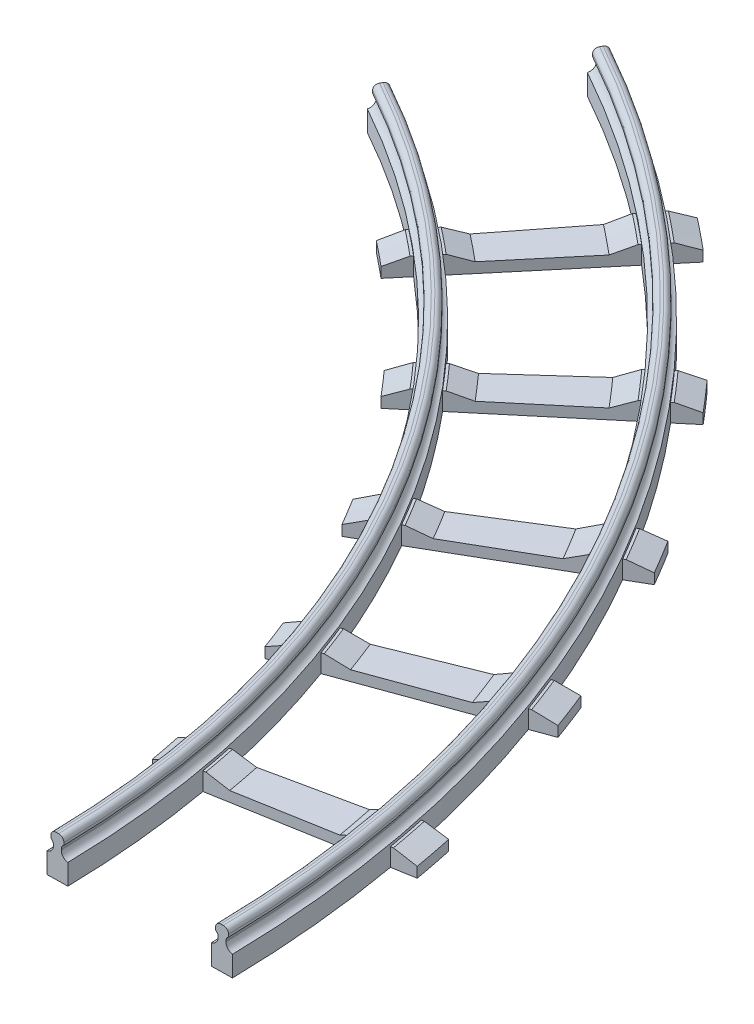
SolidWorks part; units mm, degrees
other "标注1"
sketch "草图3" plane through (-22.25, 4, -10) normal (-0.231, 0.6469, -0.7268) x (-0.9696, -0.2151, 0.1167)
other "标注2"
sketch "草图4" plane through (22.25, 8, -30) normal (0.0083, 0.0567, -0.9984) x (-0.9991, 0.0415, -0.0059)
ref_plane "前视基准面" through (0, 0, 0) normal (0, 0, 1) x (1, 0, 0)
ref_plane "上视基准面" through (0, 0, 0) normal (0, 1, 0) x (1, 0, 0)
ref_plane "右视基准面" through (0, 0, 0) normal (1, 0, 0) x (0, 0, -1)
other "Configuration Table"
sketch "草图1" plane through (0, 0, 0) normal (0, 1, 0) x (1, 0, 0)
  line L0 (-13.75, 14.5) -> (-13.75, -14.5)
  line L13 (-17.75, -14.5) -> (17.75, -14.5)
  line L21 (-17.75, -14.5) -> (-17.75, 14.5)
  line L22 (-17.75, 14.5) -> (17.75, 14.5)
  line L23 (17.75, -14.5) -> (17.75, 14.5)
  line L24 (-17.75, -14.5) -> (17.75, 14.5) construction
  line L25 (-17.75, 14.5) -> (17.75, -14.5) construction
  line L27 (13.75, 14.5) -> (13.75, -14.5)
  line L29 (-13.75, 0) -> (13.75, 0) construction
  line L32 (-22.25, 14.5) -> (22.25, 14.5)
  line L33 (-22.25, 14.5) -> (-22.25, 6.5)
  line L34 (-22.25, 6.5) -> (22.25, 6.5)
  line L35 (22.25, 14.5) -> (22.25, 6.5)
  point P0 (0, 0)
  point P15 (0, 6.5)
  dimension "D3" = 27.5
  dimension "D4" = 8
  dimension "D1" = 35.5
  dimension "D2" = 29
  dimension "D5" = 44.5
extrude "凸台-拉伸1" add sketch "草图1" along normal blind 4 contours L34 L21 L13 L0 | L34 L27 L13 L23 | L27 L34 L23 L22 | L21 L34 L0 L22 region at (-15.75, 0, -10.5) region at (-15.75, 0, 4) region at (15.75, 0, -10.5) region at (15.75, 0, 4)
extrude "凸台-拉伸2" add sketch "草图1<7>" along normal blind 3.5 contours L34 L35 L32 L33
sketch "草图1<7>" plane through (0, 0, 0) normal (0, 1, 0) x (1, 0, 0) same geometry as "草图1"
sketch "草图2" plane through (0, 0, -14.5) normal (0, 0, -1) x (-1, 0, 0)
  line L0 (18.25, 3.5) -> (22.25, 2)
  line L1 (22.25, 3.5) -> (18.25, 3.5)
  line L2 (22.25, 3.5) -> (22.25, 2)
  line L3 (22.25, 2) -> (18.25, 2) construction
  line L4 (18.25, 3.5) -> (18.25, 2) construction
  line L5 (-22.25, 2) -> (-18.25, 3.5)
  line L6 (-22.25, 3.5) -> (-18.25, 3.5)
  line L7 (-22.25, 3.5) -> (-22.25, 2)
  line L8 (-22.25, 2) -> (-18.25, 2) construction
  line L9 (-18.25, 3.5) -> (-18.25, 2) construction
  line L10 (13.75, 3.5) -> (-13.75, 3.5) construction
  line L11 (-13.25, 3.5) -> (-9.25, 3.5)
  line L12 (-13.25, 3.5) -> (-13.25, 2) construction
  line L13 (-13.25, 2) -> (-9.25, 2) construction
  line L14 (-9.25, 3.5) -> (-9.25, 2)
  line L15 (-13.75, 3.5) -> (-13.25, 3.5) construction
  line L16 (13.25, 3.5) -> (9.25, 3.5)
  line L17 (13.25, 3.5) -> (13.25, 2) construction
  line L18 (13.25, 2) -> (9.25, 2) construction
  line L19 (9.25, 3.5) -> (9.25, 2)
  line L20 (13.25, 3.5) -> (13.75, 3.5) construction
  line L21 (17.75, 3.5) -> (18.25, 3.5) construction
  line L22 (-13.25, 3.5) -> (-9.25, 2)
  line L23 (9.25, 2) -> (13.25, 3.5)
  line L24 (-9.25, 2) -> (9.25, 2)
  line L25 (-9.25, 3.5) -> (9.25, 3.5)
  line L26 (-15.75, 4) -> (-15.75, 6.5) construction
  line L27 (14.5, 8) -> (17, 8)
  line L28 (14.5, 8) -> (14.5, 6.5)
  line L29 (14.5, 6.5) -> (17, 6.5)
  line L30 (17, 8) -> (17, 6.5)
  line L31 (-17, 8) -> (-14.5, 8)
  line L32 (-17, 8) -> (-17, 6.5)
  line L33 (-17, 6.5) -> (-14.5, 6.5)
  line L34 (-14.5, 8) -> (-14.5, 6.5)
  line L35 (-13.75, 4) -> (-17.75, 4) construction
  line L36 (15.75, 6.5) -> (15.75, 4) construction
  line L37 (17.75, 4) -> (13.75, 4) construction
  line L38 (15, 6.5) -> (15, 4)
  line L39 (16.5, 6.5) -> (16.5, 4)
  line L40 (16.5, 4) -> (15.75, 4)
  line L41 (15.75, 4) -> (15, 4)
  line L42 (-16.5, 6.5) -> (-16.5, 4)
  line L43 (-16.5, 4) -> (-15.75, 4)
  line L44 (-15.75, 4) -> (-15, 4)
  line L45 (-15, 4) -> (-15, 6.5)
  line M9 (22.25, 3.5) -> (17.75, 3.5)
  line M11 (17.75, 4) -> (13.75, 4)
  line M13 (13.75, 3.5) -> (-13.75, 3.5)
  line M15 (-13.75, 4) -> (-17.75, 4)
  line M17 (-17.75, 3.5) -> (-22.25, 3.5)
  line M18 (-22.25, 3.5) -> (-22.25, 0)
  line M20 (22.25, 0) -> (22.25, 3.5)
  dimension "D1" = 4
  dimension "D2" = 1.5
  dimension "D3" = 2.5
  dimension "D4" = 1.5
  dimension "D5" = 2.5
  dimension "D6" = 1.5
extrude "切除-拉伸1" cut sketch "草图2" against normal through all contours L14 L24 L19 M13 | L19 L23 M13 | L22 L14 M13 | L5 M18 M17 | L0 M9 M20 region at (-20.9167, 3, -14.5) region at (20.9167, 3, -14.5) region at (10.5833, 3, -14.5) region at (0, 2.75, -14.5) region at (-10.5833, 3, -14.5)
extrude "凸台-拉伸4" add sketch "草图2<3>" against normal through all contours L34 L31 L32 L33 | L45 L33 L42 M15 | L30 L27 L28 L29 | L39 L29 L38 M11 region at (-15.75, 7.25, -14.5) region at (-15.75, 5.25, -14.5) region at (15.75, 7.25, -14.5) region at (15.75, 5.25, -14.5)
sketch "草图2<3>" plane through (0, 0, -14.5) normal (0, 0, -1) x (-1, 0, 0) same geometry as "草图2"
fillet "圆角1" radius 1 4 edges at (-16.5, 6.5, 0) (-15, 6.5, 0) (15, 6.5, 0) (16.5, 6.5, 0)
fillet "圆角2" radius 1.5 4 edges at (16.5, 4, 0) (15, 4, 0) (-15, 4, 0) (-16.5, 4, 0)
fillet "圆角3" radius 1 4 edges at (-17, 8, 0) (14.5, 8, 0) (17, 8, 0) (-14.5, 8, 0)
sketch "草图5" plane through (0, 0, -14.5) normal (0, 0, -1) x (-1, 0, 0)
  line L26 (17, 6.5) -> (17, 7)
  line L27 (16, 8) -> (15.5, 8)
  line L28 (14.5, 7) -> (14.5, 6.5)
  line L29 (15, 5.634) -> (15, 5.479)
  line L30 (13.75, 4) -> (13.75, 3.5)
  line L31 (13.75, 3.5) -> (13.25, 3.5)
  line L32 (13.25, 3.5) -> (9.25, 2)
  line L33 (9.25, 2) -> (-9.25, 2)
  line L34 (-9.25, 2) -> (-13.25, 3.5)
  line L35 (-13.25, 3.5) -> (-13.75, 3.5)
  line L36 (-13.75, 3.5) -> (-13.75, 4)
  line L37 (-15, 5.479) -> (-15, 5.634)
  line L38 (-14.5, 6.5) -> (-14.5, 7)
  line L39 (-15.5, 8) -> (-16, 8)
  line L40 (-17, 7) -> (-17, 6.5)
  line L41 (-16.5, 5.634) -> (-16.5, 5.479)
  line L42 (-17.75, 4) -> (-17.75, 3.5)
  line L43 (-17.75, 3.5) -> (-18.25, 3.5)
  line L44 (-18.25, 3.5) -> (-22.25, 2)
  line L45 (-22.25, 2) -> (-22.25, 0)
  line L46 (-22.25, 0) -> (22.25, 0)
  line L47 (22.25, 0) -> (22.25, 2)
  line L48 (22.25, 2) -> (18.25, 3.5)
  line L49 (18.25, 3.5) -> (17.75, 3.5)
  line L50 (17.75, 3.5) -> (17.75, 4)
  line L51 (16.5, 5.479) -> (16.5, 5.634)
  line L52 (17, 6.5) -> (17, 7)
  line L53 (16, 8) -> (15.5, 8)
  line L54 (14.5, 7) -> (14.5, 6.5)
  line L55 (15, 5.634) -> (15, 5.479)
  line L56 (13.75, 4) -> (13.75, 3.5)
  line L57 (13.75, 3.5) -> (13.25, 3.5)
  line L58 (13.25, 3.5) -> (9.25, 2)
  line L59 (9.25, 2) -> (-9.25, 2)
  line L60 (-9.25, 2) -> (-13.25, 3.5)
  line L61 (-13.25, 3.5) -> (-13.75, 3.5)
  line L62 (-13.75, 3.5) -> (-13.75, 4)
  line L63 (-15, 5.479) -> (-15, 5.634)
  line L64 (-14.5, 6.5) -> (-14.5, 7)
  line L65 (-15.5, 8) -> (-16, 8)
  line L66 (-17, 7) -> (-17, 6.5)
  line L67 (-16.5, 5.634) -> (-16.5, 5.479)
  line L68 (-17.75, 4) -> (-17.75, 3.5)
  line L69 (-17.75, 3.5) -> (-18.25, 3.5)
  line L70 (-18.25, 3.5) -> (-22.25, 2)
  line L71 (-22.25, 2) -> (-22.25, 0)
  line L72 (-22.25, 0) -> (22.25, 0)
  line L73 (22.25, 0) -> (22.25, 2)
  line L74 (22.25, 2) -> (18.25, 3.5)
  line L75 (18.25, 3.5) -> (17.75, 3.5)
  line L76 (17.75, 3.5) -> (17.75, 4)
  line L77 (16.5, 5.479) -> (16.5, 5.634)
  arc A12 (17, 7) -> (16, 8) centre (16, 7) ccw
  arc A13 (15.5, 8) -> (14.5, 7) centre (15.5, 7) ccw
  arc A14 (15, 5.634) -> (14.5, 6.5) centre (14, 5.634) ccw
  arc A15 (13.75, 4) -> (15, 5.479) centre (13.5, 5.479) ccw
  arc A16 (-15, 5.479) -> (-13.75, 4) centre (-13.5, 5.479) ccw
  arc A17 (-14.5, 6.5) -> (-15, 5.634) centre (-14, 5.634) ccw
  arc A18 (-14.5, 7) -> (-15.5, 8) centre (-15.5, 7) ccw
  arc A19 (-16, 8) -> (-17, 7) centre (-16, 7) ccw
  arc A20 (-16.5, 5.634) -> (-17, 6.5) centre (-17.5, 5.634) ccw
  arc A21 (-17.75, 4) -> (-16.5, 5.479) centre (-18, 5.479) ccw
  arc A22 (16.5, 5.479) -> (17.75, 4) centre (18, 5.479) ccw
  arc A23 (17, 6.5) -> (16.5, 5.634) centre (17.5, 5.634) ccw
  arc A24 (17, 7) -> (16, 8) centre (16, 7) ccw
  arc A25 (15.5, 8) -> (14.5, 7) centre (15.5, 7) ccw
  arc A26 (15, 5.634) -> (14.5, 6.5) centre (14, 5.634) ccw
  arc A27 (13.75, 4) -> (15, 5.479) centre (13.5, 5.479) ccw
  arc A28 (-15, 5.479) -> (-13.75, 4) centre (-13.5, 5.479) ccw
  arc A29 (-14.5, 6.5) -> (-15, 5.634) centre (-14, 5.634) ccw
  arc A30 (-14.5, 7) -> (-15.5, 8) centre (-15.5, 7) ccw
  arc A31 (-16, 8) -> (-17, 7) centre (-16, 7) ccw
  arc A32 (-16.5, 5.634) -> (-17, 6.5) centre (-17.5, 5.634) ccw
  arc A33 (-17.75, 4) -> (-16.5, 5.479) centre (-18, 5.479) ccw
  arc A34 (16.5, 5.479) -> (17.75, 4) centre (18, 5.479) ccw
  arc A35 (17, 6.5) -> (16.5, 5.634) centre (17.5, 5.634) ccw
  dimension "D1" = 0
sketch "草图7" plane through (0, 0, -14.5) normal (0, 0, -1) x (-1, 0, 0)
  line L0 (-17.75, 3.5) -> (-17.75, 0)
  line L1 (-13.75, 3.5) -> (-13.75, 0)
  line L2 (13.75, 3.5) -> (13.75, 0)
  line L3 (17.75, 3.5) -> (17.75, 0)
  line L4 (13.75, 0) -> (17.75, 0)
  line L26 (17, 6.5) -> (17, 7)
  line L27 (16, 8) -> (15.5, 8)
  line L28 (14.5, 7) -> (14.5, 6.5)
  line L29 (15, 5.634) -> (15, 5.479)
  line L30 (13.75, 4) -> (13.75, 3.5)
  line L31 (13.75, 3.5) -> (13.25, 3.5)
  line L32 (13.25, 3.5) -> (9.25, 2)
  line L33 (9.25, 2) -> (-9.25, 2)
  line L34 (-9.25, 2) -> (-13.25, 3.5)
  line L35 (-13.25, 3.5) -> (-13.75, 3.5)
  line L36 (-13.75, 3.5) -> (-13.75, 4)
  line L37 (-15, 5.479) -> (-15, 5.634)
  line L38 (-14.5, 6.5) -> (-14.5, 7)
  line L39 (-15.5, 8) -> (-16, 8)
  line L40 (-17, 7) -> (-17, 6.5)
  line L41 (-16.5, 5.634) -> (-16.5, 5.479)
  line L42 (-17.75, 4) -> (-17.75, 3.5)
  line L43 (-17.75, 3.5) -> (-18.25, 3.5)
  line L44 (-18.25, 3.5) -> (-22.25, 2)
  line L45 (-22.25, 2) -> (-22.25, 0)
  line L46 (-22.25, 0) -> (22.25, 0)
  line L47 (22.25, 0) -> (22.25, 2)
  line L48 (22.25, 2) -> (18.25, 3.5)
  line L49 (18.25, 3.5) -> (17.75, 3.5)
  line L50 (17.75, 3.5) -> (17.75, 4)
  line L51 (16.5, 5.479) -> (16.5, 5.634)
  line L52 (17, 6.5) -> (17, 7)
  line L53 (16, 8) -> (15.5, 8)
  line L54 (14.5, 7) -> (14.5, 6.5)
  line L55 (15, 5.634) -> (15, 5.479)
  line L56 (13.75, 4) -> (13.75, 3.5)
  line L62 (-13.75, 3.5) -> (-13.75, 4)
  line L63 (-15, 5.479) -> (-15, 5.634)
  line L64 (-14.5, 6.5) -> (-14.5, 7)
  line L65 (-15.5, 8) -> (-16, 8)
  line L66 (-17, 7) -> (-17, 6.5)
  line L67 (-16.5, 5.634) -> (-16.5, 5.479)
  line L68 (-17.75, 4) -> (-17.75, 3.5)
  line L72 (-17.75, 0) -> (-13.75, 0)
  line L76 (17.75, 3.5) -> (17.75, 4)
  line L77 (16.5, 5.479) -> (16.5, 5.634)
  arc A12 (17, 7) -> (16, 8) centre (16, 7) ccw
  arc A13 (15.5, 8) -> (14.5, 7) centre (15.5, 7) ccw
  arc A14 (15, 5.634) -> (14.5, 6.5) centre (14, 5.634) ccw
  arc A15 (13.75, 4) -> (15, 5.479) centre (13.5, 5.479) ccw
  arc A16 (-15, 5.479) -> (-13.75, 4) centre (-13.5, 5.479) ccw
  arc A17 (-14.5, 6.5) -> (-15, 5.634) centre (-14, 5.634) ccw
  arc A18 (-14.5, 7) -> (-15.5, 8) centre (-15.5, 7) ccw
  arc A19 (-16, 8) -> (-17, 7) centre (-16, 7) ccw
  arc A20 (-16.5, 5.634) -> (-17, 6.5) centre (-17.5, 5.634) ccw
  arc A21 (-17.75, 4) -> (-16.5, 5.479) centre (-18, 5.479) ccw
  arc A22 (16.5, 5.479) -> (17.75, 4) centre (18, 5.479) ccw
  arc A23 (17, 6.5) -> (16.5, 5.634) centre (17.5, 5.634) ccw
  arc A24 (17, 7) -> (16, 8) centre (16, 7) ccw
  arc A25 (15.5, 8) -> (14.5, 7) centre (15.5, 7) ccw
  arc A26 (15, 5.634) -> (14.5, 6.5) centre (14, 5.634) ccw
  arc A27 (13.75, 4) -> (15, 5.479) centre (13.5, 5.479) ccw
  arc A28 (-15, 5.479) -> (-13.75, 4) centre (-13.5, 5.479) ccw
  arc A29 (-14.5, 6.5) -> (-15, 5.634) centre (-14, 5.634) ccw
  arc A30 (-14.5, 7) -> (-15.5, 8) centre (-15.5, 7) ccw
  arc A31 (-16, 8) -> (-17, 7) centre (-16, 7) ccw
  arc A32 (-16.5, 5.634) -> (-17, 6.5) centre (-17.5, 5.634) ccw
  arc A33 (-17.75, 4) -> (-16.5, 5.479) centre (-18, 5.479) ccw
  arc A34 (16.5, 5.479) -> (17.75, 4) centre (18, 5.479) ccw
  arc A35 (17, 6.5) -> (16.5, 5.634) centre (17.5, 5.634) ccw
  dimension "D1" = 0
sketch "草图6" plane through (0, 0, -14.5) normal (0, 0, -1) x (-1, 0, 0)
  line L0 (0, 0) -> (200, 0) construction
  line L1 (200, 10) -> (200, -10)
  dimension "D1" = 200
  dimension "D2" = 20
revolve "旋转2" add sketch "草图7" angle 62 about L1 reverse direction yes
extrude "切除-拉伸5" cut sketch "草图5<2>" against normal through all
sketch "草图5<2>" plane through (0, 0, -14.5) normal (0, 0, -1) x (-1, 0, 0) same geometry as "草图5"
revolve "旋转1" add sketch "草图5" angle 2 about L1 reverse direction yes
pattern_circular "阵列(圆周)1" count 7 every 10 about axis through (-200, 10, -14.5) along (0, -1, 0) of "旋转1" reverse direction yes
sketch "草图8" plane through (0, 0, -14.5) normal (0, 0, 1) x (1, 0, 0)
  line L78 (-22.25, 2) -> (-22.25, 0)
  line L79 (-22.25, 0) -> (22.25, 0)
  line L80 (22.25, 0) -> (22.25, 2)
  line L81 (22.25, 2) -> (18.25, 3.5)
  line L82 (18.25, 3.5) -> (17.75, 3.5)
  line L83 (17.75, 3.5) -> (17.75, 4)
  line L84 (16.5, 5.479) -> (16.5, 5.634)
  line L85 (17, 6.5) -> (17, 7)
  line L86 (16, 8) -> (15.5, 8)
  line L87 (14.5, 7) -> (14.5, 6.5)
  line L88 (15, 5.634) -> (15, 5.479)
  line L89 (13.75, 4) -> (13.75, 3.5)
  line L90 (13.75, 3.5) -> (13.25, 3.5)
  line L91 (13.25, 3.5) -> (9.25, 2)
  line L92 (9.25, 2) -> (-9.25, 2)
  line L93 (-9.25, 2) -> (-13.25, 3.5)
  line L94 (-13.25, 3.5) -> (-13.75, 3.5)
  line L95 (-13.75, 3.5) -> (-13.75, 4)
  line L96 (-15, 5.479) -> (-15, 5.634)
  line L97 (-14.5, 6.5) -> (-14.5, 7)
  line L98 (-15.5, 8) -> (-16, 8)
  line L99 (-17, 7) -> (-17, 6.5)
  line L100 (-16.5, 5.634) -> (-16.5, 5.479)
  line L101 (-17.75, 4) -> (-17.75, 3.5)
  line L102 (-17.75, 3.5) -> (-18.25, 3.5)
  line L103 (-18.25, 3.5) -> (-22.25, 2)
  line L104 (-22.25, 2) -> (-22.25, 0)
  line L105 (-22.25, 0) -> (22.25, 0)
  line L106 (22.25, 0) -> (22.25, 2)
  line L107 (22.25, 2) -> (18.25, 3.5)
  line L108 (18.25, 3.5) -> (17.75, 3.5)
  line L109 (17.75, 3.5) -> (17.75, 4)
  line L110 (16.5, 5.479) -> (16.5, 5.634)
  line L111 (17, 6.5) -> (17, 7)
  line L112 (16, 8) -> (15.5, 8)
  line L113 (14.5, 7) -> (14.5, 6.5)
  line L114 (15, 5.634) -> (15, 5.479)
  line L115 (13.75, 4) -> (13.75, 3.5)
  line L116 (13.75, 3.5) -> (13.25, 3.5)
  line L117 (13.25, 3.5) -> (9.25, 2)
  line L118 (9.25, 2) -> (-9.25, 2)
  line L119 (-9.25, 2) -> (-13.25, 3.5)
  line L120 (-13.25, 3.5) -> (-13.75, 3.5)
  line L121 (-13.75, 3.5) -> (-13.75, 4)
  line L122 (-15, 5.479) -> (-15, 5.634)
  line L123 (-14.5, 6.5) -> (-14.5, 7)
  line L124 (-15.5, 8) -> (-16, 8)
  line L125 (-17, 7) -> (-17, 6.5)
  line L126 (-16.5, 5.634) -> (-16.5, 5.479)
  line L127 (-17.75, 4) -> (-17.75, 3.5)
  line L128 (-17.75, 3.5) -> (-18.25, 3.5)
  line L129 (-18.25, 3.5) -> (-22.25, 2)
  arc A36 (16.5, 5.479) -> (17.75, 4) centre (18, 5.479) ccw
  arc A37 (17, 6.5) -> (16.5, 5.634) centre (17.5, 5.634) ccw
  arc A38 (17, 7) -> (16, 8) centre (16, 7) ccw
  arc A39 (15.5, 8) -> (14.5, 7) centre (15.5, 7) ccw
  arc A40 (15, 5.634) -> (14.5, 6.5) centre (14, 5.634) ccw
  arc A41 (13.75, 4) -> (15, 5.479) centre (13.5, 5.479) ccw
  arc A42 (-15, 5.479) -> (-13.75, 4) centre (-13.5, 5.479) ccw
  arc A43 (-14.5, 6.5) -> (-15, 5.634) centre (-14, 5.634) ccw
  arc A44 (-14.5, 7) -> (-15.5, 8) centre (-15.5, 7) ccw
  arc A45 (-16, 8) -> (-17, 7) centre (-16, 7) ccw
  arc A46 (-16.5, 5.634) -> (-17, 6.5) centre (-17.5, 5.634) ccw
  arc A47 (-17.75, 4) -> (-16.5, 5.479) centre (-18, 5.479) ccw
  arc A48 (16.5, 5.479) -> (17.75, 4) centre (18, 5.479) ccw
  arc A49 (17, 6.5) -> (16.5, 5.634) centre (17.5, 5.634) ccw
  arc A50 (17, 7) -> (16, 8) centre (16, 7) ccw
  arc A51 (15.5, 8) -> (14.5, 7) centre (15.5, 7) ccw
  arc A52 (15, 5.634) -> (14.5, 6.5) centre (14, 5.634) ccw
  arc A53 (13.75, 4) -> (15, 5.479) centre (13.5, 5.479) ccw
  arc A54 (-15, 5.479) -> (-13.75, 4) centre (-13.5, 5.479) ccw
  arc A55 (-14.5, 6.5) -> (-15, 5.634) centre (-14, 5.634) ccw
  arc A56 (-14.5, 7) -> (-15.5, 8) centre (-15.5, 7) ccw
  arc A57 (-16, 8) -> (-17, 7) centre (-16, 7) ccw
  arc A58 (-16.5, 5.634) -> (-17, 6.5) centre (-17.5, 5.634) ccw
  arc A59 (-17.75, 4) -> (-16.5, 5.479) centre (-18, 5.479) ccw
  dimension "D1" = 0
revolve "切除-旋转1" cut sketch "草图8" angle 1 about L1 reverse direction yes
sketch "草图9" plane through (-161.9298, 0, -86.0996) normal (-0.8829, 0, -0.4695) x (-0.4695, 0, 0.8829)
  line L8 (-141.1584, 0) -> (-96.6584, 0)
  line L10 (-141.1584, 0) -> (-96.6584, 0)
  line L12 (-101.1584, 3.5) -> (-101.1584, 4)
  line L14 (-101.1584, 3.5) -> (-101.1584, 4)
  line L16 (-102.4084, 5.479) -> (-102.4084, 5.634)
  line L18 (-102.4084, 5.479) -> (-102.4084, 5.634)
  line L20 (-101.9084, 6.5) -> (-101.9084, 7)
  line L22 (-101.9084, 6.5) -> (-101.9084, 7)
  line L42 (-102.9084, 8) -> (-103.4084, 8)
  line L43 (-102.9084, 8) -> (-103.4084, 8)
  line L44 (-104.4084, 7) -> (-104.4084, 6.5)
  line L45 (-104.4084, 7) -> (-104.4084, 6.5)
  line L46 (-103.9084, 5.634) -> (-103.9084, 5.479)
  line L47 (-103.9084, 5.634) -> (-103.9084, 5.479)
  line L48 (-105.1584, 4) -> (-105.1584, 3.5)
  line L49 (-105.1584, 4) -> (-105.1584, 3.5)
  line L50 (-132.6584, 3.5) -> (-132.6584, 4)
  line L51 (-132.6584, 3.5) -> (-132.6584, 4)
  line L78 (-133.9084, 5.479) -> (-133.9084, 5.634)
  line L79 (-133.9084, 5.479) -> (-133.9084, 5.634)
  line L80 (-133.4084, 6.5) -> (-133.4084, 7)
  line L81 (-133.4084, 6.5) -> (-133.4084, 7)
  line L82 (-134.4084, 8) -> (-134.9084, 8)
  line L83 (-134.4084, 8) -> (-134.9084, 8)
  line L84 (-135.9084, 7) -> (-135.9084, 6.5)
  line L85 (-135.9084, 7) -> (-135.9084, 6.5)
  line L86 (-135.4084, 5.634) -> (-135.4084, 5.479)
  line L87 (-135.4084, 5.634) -> (-135.4084, 5.479)
  line L88 (-136.6584, 4) -> (-136.6584, 3.5)
  line L89 (-136.6584, 4) -> (-136.6584, 3.5)
  line L90 (-96.6584, 0) -> (-96.6584, 2)
  line L92 (-96.6584, 0) -> (-96.6584, 2)
  line L94 (-96.6584, 2) -> (-100.6584, 3.5)
  line L96 (-96.6584, 2) -> (-100.6584, 3.5)
  line L98 (-100.6584, 3.5) -> (-101.1584, 3.5)
  line L100 (-100.6584, 3.5) -> (-101.1584, 3.5)
  line L102 (-105.1584, 3.5) -> (-105.6584, 3.5)
  line L104 (-105.1584, 3.5) -> (-105.6584, 3.5)
  line L106 (-105.6584, 3.5) -> (-109.6584, 2)
  line L108 (-105.6584, 3.5) -> (-109.6584, 2)
  line L110 (-109.6584, 2) -> (-128.1584, 2)
  line L112 (-109.6584, 2) -> (-128.1584, 2)
  line L113 (-128.1584, 2) -> (-132.1584, 3.5)
  line L114 (-128.1584, 2) -> (-132.1584, 3.5)
  line L115 (-132.1584, 3.5) -> (-132.6584, 3.5)
  line L116 (-132.1584, 3.5) -> (-132.6584, 3.5)
  line L117 (-136.6584, 3.5) -> (-137.1584, 3.5)
  line L118 (-136.6584, 3.5) -> (-137.1584, 3.5)
  line L119 (-137.1584, 3.5) -> (-141.1584, 2)
  line L120 (-137.1584, 3.5) -> (-141.1584, 2)
  line L121 (-141.1584, 2) -> (-141.1584, 0)
  line L122 (-141.1584, 2) -> (-141.1584, 0)
  arc A6 (-102.4084, 5.479) -> (-101.1584, 4) centre (-100.9084, 5.479) ccw
  arc A8 (-102.4084, 5.479) -> (-101.1584, 4) centre (-100.9084, 5.479) ccw
  arc A10 (-101.9084, 6.5) -> (-102.4084, 5.634) centre (-101.4084, 5.634) ccw
  arc A12 (-101.9084, 6.5) -> (-102.4084, 5.634) centre (-101.4084, 5.634) ccw
  arc A14 (-101.9084, 7) -> (-102.9084, 8) centre (-102.9084, 7) ccw
  arc A16 (-101.9084, 7) -> (-102.9084, 8) centre (-102.9084, 7) ccw
  arc A36 (-103.4084, 8) -> (-104.4084, 7) centre (-103.4084, 7) ccw
  arc A37 (-103.4084, 8) -> (-104.4084, 7) centre (-103.4084, 7) ccw
  arc A38 (-103.9084, 5.634) -> (-104.4084, 6.5) centre (-104.9084, 5.634) ccw
  arc A39 (-103.9084, 5.634) -> (-104.4084, 6.5) centre (-104.9084, 5.634) ccw
  arc A40 (-105.1584, 4) -> (-103.9084, 5.479) centre (-105.4084, 5.479) ccw
  arc A41 (-105.1584, 4) -> (-103.9084, 5.479) centre (-105.4084, 5.479) ccw
  arc A42 (-133.9084, 5.479) -> (-132.6584, 4) centre (-132.4084, 5.479) ccw
  arc A43 (-133.9084, 5.479) -> (-132.6584, 4) centre (-132.4084, 5.479) ccw
  arc A44 (-133.4084, 6.5) -> (-133.9084, 5.634) centre (-132.9084, 5.634) ccw
  arc A45 (-133.4084, 6.5) -> (-133.9084, 5.634) centre (-132.9084, 5.634) ccw
  arc A46 (-133.4084, 7) -> (-134.4084, 8) centre (-134.4084, 7) ccw
  arc A47 (-133.4084, 7) -> (-134.4084, 8) centre (-134.4084, 7) ccw
  arc A48 (-134.9084, 8) -> (-135.9084, 7) centre (-134.9084, 7) ccw
  arc A49 (-134.9084, 8) -> (-135.9084, 7) centre (-134.9084, 7) ccw
  arc A50 (-135.4084, 5.634) -> (-135.9084, 6.5) centre (-136.4084, 5.634) ccw
  arc A51 (-135.4084, 5.634) -> (-135.9084, 6.5) centre (-136.4084, 5.634) ccw
  arc A52 (-136.6584, 4) -> (-135.4084, 5.479) centre (-136.9084, 5.479) ccw
  arc A53 (-136.6584, 4) -> (-135.4084, 5.479) centre (-136.9084, 5.479) ccw
  dimension "D1" = 0
revolve "切除-旋转2" cut sketch "草图9" angle 1 about L1
sketch "草图10" plane through (-0.3139, 0, -17.9855) normal (0.0175, 0, 0.9998) x (0.9998, 0, -0.0175)
  line L0 (-17.4665, 3.5) -> (-17.4665, 0)
  line L1 (-13.4665, 3.5) -> (-13.4665, 0)
  line L2 (14.0335, 3.5) -> (14.0335, 0)
  line L3 (18.0335, 3.5) -> (18.0335, 0)
  line L4 (-13.4665, 0) -> (14.0335, 0)
  line L5 (18.0335, 0) -> (22.5335, 0)
  line L26 (-17.9665, 3.5) -> (-21.9665, 2)
  line L27 (-21.9665, 2) -> (-21.9665, 0)
  line L28 (-21.9665, 0) -> (22.5335, 0)
  line L29 (22.5335, 0) -> (22.5335, 2)
  line L30 (22.5335, 2) -> (18.5335, 3.5)
  line L31 (18.5335, 3.5) -> (18.0335, 3.5)
  line L32 (18.0335, 3.5) -> (18.0335, 4)
  line L33 (16.7835, 5.479) -> (16.7835, 5.634)
  line L34 (17.2835, 6.5) -> (17.2835, 7)
  line L35 (16.2835, 8) -> (15.7835, 8)
  line L36 (14.7835, 7) -> (14.7835, 6.5)
  line L37 (15.2835, 5.634) -> (15.2835, 5.479)
  line L38 (14.0335, 4) -> (14.0335, 3.5)
  line L39 (14.0335, 3.5) -> (13.5335, 3.5)
  line L40 (13.5335, 3.5) -> (9.5335, 2)
  line L41 (9.5335, 2) -> (-8.9665, 2)
  line L42 (-8.9665, 2) -> (-12.9665, 3.5)
  line L43 (-12.9665, 3.5) -> (-13.4665, 3.5)
  line L44 (-13.4665, 3.5) -> (-13.4665, 4)
  line L45 (-14.7165, 5.479) -> (-14.7165, 5.634)
  line L46 (-14.2165, 6.5) -> (-14.2165, 7)
  line L47 (-15.2165, 8) -> (-15.7165, 8)
  line L48 (-16.7165, 7) -> (-16.7165, 6.5)
  line L49 (-16.2165, 5.634) -> (-16.2165, 5.479)
  line L50 (-17.4665, 4) -> (-17.4665, 3.5)
  line L51 (-17.4665, 3.5) -> (-17.9665, 3.5)
  line L52 (-17.9665, 3.5) -> (-21.9665, 2)
  line L53 (-21.9665, 2) -> (-21.9665, 0)
  line L54 (-21.9665, 0) -> (-17.4665, 0)
  line L55 (22.5335, 0) -> (22.5335, 2)
  line L56 (22.5335, 2) -> (18.5335, 3.5)
  line L57 (18.5335, 3.5) -> (18.0335, 3.5)
  line L65 (14.0335, 3.5) -> (13.5335, 3.5)
  line L66 (13.5335, 3.5) -> (9.5335, 2)
  line L67 (9.5335, 2) -> (-8.9665, 2)
  line L68 (-8.9665, 2) -> (-12.9665, 3.5)
  line L69 (-12.9665, 3.5) -> (-13.4665, 3.5)
  line L77 (-17.4665, 3.5) -> (-17.9665, 3.5)
  arc A12 (16.7835, 5.479) -> (18.0335, 4) centre (18.2835, 5.479) ccw
  arc A13 (17.2835, 6.5) -> (16.7835, 5.634) centre (17.7835, 5.634) ccw
  arc A14 (17.2835, 7) -> (16.2835, 8) centre (16.2835, 7) ccw
  arc A15 (15.7835, 8) -> (14.7835, 7) centre (15.7835, 7) ccw
  arc A16 (15.2835, 5.634) -> (14.7835, 6.5) centre (14.2835, 5.634) ccw
  arc A17 (14.0335, 4) -> (15.2835, 5.479) centre (13.7835, 5.479) ccw
  arc A18 (-14.7165, 5.479) -> (-13.4665, 4) centre (-13.2165, 5.479) ccw
  arc A19 (-14.2165, 6.5) -> (-14.7165, 5.634) centre (-13.7165, 5.634) ccw
  arc A20 (-14.2165, 7) -> (-15.2165, 8) centre (-15.2165, 7) ccw
  arc A21 (-15.7165, 8) -> (-16.7165, 7) centre (-15.7165, 7) ccw
  arc A22 (-16.2165, 5.634) -> (-16.7165, 6.5) centre (-17.2165, 5.634) ccw
  arc A23 (-17.4665, 4) -> (-16.2165, 5.479) centre (-17.7165, 5.479) ccw
  dimension "D1" = 0
revolve "切除-旋转3" cut sketch "草图10" angle 1 about L1 reverse direction yes
sketch "草图11" plane through (-159.1403, 0, -88.2129) normal (-0.8746, 0, -0.4848) x (-0.4848, 0, 0.8746)
  line L6 (-133.4701, 3.5) -> (-133.4701, 0)
  line L7 (-137.9701, 0) -> (-93.4701, 0) construction
  line L8 (-133.4701, 0) -> (-137.9701, 0)
  line L9 (-129.4701, 3.5) -> (-129.4701, 0)
  line L10 (-129.4701, 0) -> (-101.9701, 0)
  line L11 (-101.9701, 0) -> (-101.9701, 3.5)
  line L12 (-97.9701, 3.5) -> (-97.9701, 0)
  line L13 (-97.9701, 0) -> (-93.4701, 0)
  line L14 (-129.4701, 3.5) -> (-129.4701, 4) construction
  line L27 (-137.9701, 0) -> (-93.4701, 0)
  line L31 (-97.9701, 3.5) -> (-97.9701, 4)
  line L32 (-99.2201, 5.479) -> (-99.2201, 5.634)
  line L33 (-98.7201, 6.5) -> (-98.7201, 7)
  line L34 (-99.7201, 8) -> (-100.2201, 8)
  line L35 (-101.2201, 7) -> (-101.2201, 6.5)
  line L36 (-100.7201, 5.634) -> (-100.7201, 5.479)
  line L37 (-101.9701, 4) -> (-101.9701, 3.5)
  line L40 (-129.4701, 3.5) -> (-129.4701, 4)
  line L41 (-130.7201, 5.479) -> (-130.7201, 5.634)
  line L42 (-130.2201, 6.5) -> (-130.2201, 7)
  line L43 (-131.2201, 8) -> (-131.7201, 8)
  line L44 (-132.7201, 7) -> (-132.7201, 6.5)
  line L45 (-132.2201, 5.634) -> (-132.2201, 5.479)
  line L46 (-133.4701, 4) -> (-133.4701, 3.5)
  line L49 (-137.9701, 2) -> (-137.9701, 0)
  line L51 (-137.9701, 2) -> (-137.9701, 0)
  line L79 (-93.4701, 0) -> (-93.4701, 2)
  line L81 (-93.4701, 0) -> (-93.4701, 2)
  line L83 (-93.4701, 2) -> (-97.4701, 3.5)
  line L85 (-93.4701, 2) -> (-97.4701, 3.5)
  line L87 (-97.4701, 3.5) -> (-97.9701, 3.5)
  line L89 (-97.4701, 3.5) -> (-97.9701, 3.5)
  line L91 (-101.9701, 3.5) -> (-102.4701, 3.5)
  line L93 (-101.9701, 3.5) -> (-102.4701, 3.5)
  line L104 (-102.4701, 3.5) -> (-106.4701, 2)
  line L105 (-102.4701, 3.5) -> (-106.4701, 2)
  line L106 (-106.4701, 2) -> (-124.9701, 2)
  line L107 (-106.4701, 2) -> (-124.9701, 2)
  line L108 (-124.9701, 2) -> (-128.9701, 3.5)
  line L109 (-124.9701, 2) -> (-128.9701, 3.5)
  line L110 (-128.9701, 3.5) -> (-129.4701, 3.5)
  line L111 (-128.9701, 3.5) -> (-129.4701, 3.5)
  line L112 (-133.4701, 3.5) -> (-133.9701, 3.5)
  line L113 (-133.4701, 3.5) -> (-133.9701, 3.5)
  line L114 (-133.9701, 3.5) -> (-137.9701, 2)
  line L115 (-133.9701, 3.5) -> (-137.9701, 2)
  arc A12 (-99.2201, 5.479) -> (-97.9701, 4) centre (-97.7201, 5.479) ccw
  arc A13 (-98.7201, 6.5) -> (-99.2201, 5.634) centre (-98.2201, 5.634) ccw
  arc A14 (-98.7201, 7) -> (-99.7201, 8) centre (-99.7201, 7) ccw
  arc A15 (-100.2201, 8) -> (-101.2201, 7) centre (-100.2201, 7) ccw
  arc A16 (-100.7201, 5.634) -> (-101.2201, 6.5) centre (-101.7201, 5.634) ccw
  arc A17 (-101.9701, 4) -> (-100.7201, 5.479) centre (-102.2201, 5.479) ccw
  arc A18 (-130.7201, 5.479) -> (-129.4701, 4) centre (-129.2201, 5.479) ccw
  arc A19 (-130.2201, 6.5) -> (-130.7201, 5.634) centre (-129.7201, 5.634) ccw
  arc A20 (-130.2201, 7) -> (-131.2201, 8) centre (-131.2201, 7) ccw
  arc A21 (-131.7201, 8) -> (-132.7201, 7) centre (-131.7201, 7) ccw
  arc A22 (-132.2201, 5.634) -> (-132.7201, 6.5) centre (-133.2201, 5.634) ccw
  arc A23 (-133.4701, 4) -> (-132.2201, 5.479) centre (-133.7201, 5.479) ccw
  dimension "D1" = 0
revolve "切除-旋转4" cut sketch "草图11" angle 1 about L1 region at (-93.4465, 1.4559, -206.7277) region at (-103.0381, 1.186, -189.4239) region at (-112.6297, 1.4559, -172.1202)
